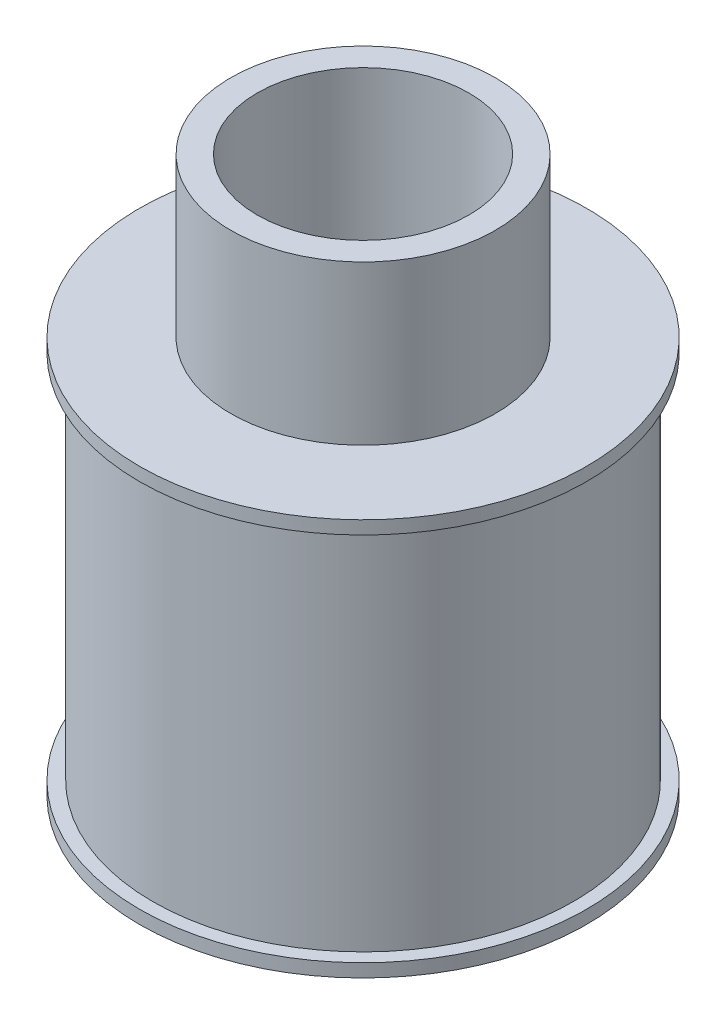
SolidWorks part; units mm, degrees
note: '?' marks a value the reader was unsure of. The reader was unsure of these and kept them because the rebuilt part matched: shared geometry of "Croquis2<2>".
ref_plane "Alzado" through (0, 0, 0) normal (1, 0, 0) x (0, 1, 0)
ref_plane "Planta" through (0, 0, 0) normal (0, 0, 1) x (0, 1, 0)
ref_plane "Vista lateral" through (0, 0, 0) normal (0, 1, 0) x (-1, 0, 0)
sketch "Croquis1" plane through (0, 0, 0) normal (0, 1, 0) x (-1, 0, 0)
  circle A0 centre (0, 0) radius 7.95
  dimension "D1" = 15.9
extrude "Saliente-Extruir1" add sketch "Croquis1" along normal mid plane 15
sketch "Croquis2" plane through (0, 7.5, 0) normal (0, 1, 0) x (-1, 0, 0)
  circle A3 centre (0, 0) radius 8.45
  dimension "D1" = 16.9
extrude "Saliente-Extruir2" add sketch "Croquis2" against normal blind 0.5
extrude "Saliente-Extruir3" add sketch "Croquis2<2>" along normal blind 0.5 from surface at -15 starting at face at (0, -7.5, 7.95)
sketch "Croquis2<2>" plane through (0, 7.5, 0) normal (0, 1, 0) x (-1, 0, 0) same geometry as "Croquis2"
sketch "Croquis3" plane through (0, -7.5, 0) normal (0, 1, 0) x (-1, 0, 0)
  circle A0 centre (0, 0) radius 5
  dimension "D1" = 10
extrude "Saliente-Extruir4" add sketch "Croquis3" along normal blind 21
sketch "Croquis4" plane through (0, -7, 0) normal (0, 1, 0) x (-1, 0, 0)
  circle A0 centre (0, 0) radius 3
  dimension "D1" = 6
extrude "Cortar-Extruir1" cut sketch "Croquis4" against normal through all both and the other way through all
sketch "Croquis5" [suppressed] plane through (0, 0, 0) normal (0, 0, 1) x (0, 1, 0)
  line L4 (10.5, 5) -> (10.5, -5) construction
  line L5 (13.5, 5) -> (7.5, 5) construction
  line L9 (7.5, -5) -> (7.5, 5) construction
  line L10 (7.5, -5) -> (7.5, 5) construction
  point P10 (10.5, 0)
sketch "Croquis6" [suppressed] plane through (0, 0, 0) normal (1, 0, 0) x (0, 1, 0)
  point P0 (10.5, 0)
hole_wizard "Taladro roscado M32" [suppressed] positions "Croquis6" profile "Croquis7" tap size "M3" standard "DIN"
sketch "Croquis7" plane through (0, 10.5, 0) normal (0, 1, 0) x (0, 0, 1)
  line L0 (0, 0) -> (0, 5)
  line L1 (0, 5) -> (1.25, 5)
  line L2 (1.25, 5) -> (1.25, 0)
  line L5 (1.25, 0) -> (0, 0)
  line L11 (0, -6.35) -> (0, 107.95) construction
  dimension "Diámetro de perforador para roscar hasta el siguiente" = 2.5
  dimension "Profundidad de perforador para roscar hasta el siguiente" = 5
cosmetic thread "Rosca de taladro1" [suppressed] parameters "D2"=3
hole_wizard "Taladro roscado M31" [suppressed] positions "Croquis5" profile "Croquis9" tap size "M3" standard "DIN"
sketch "Croquis9" plane through (0, 10.5, 0) normal (1, 0, 0) x (0, 1, 0)
  line L0 (0, 0) -> (0, 8.45)
  line L1 (0, 8.45) -> (1.25, 8.45)
  line L2 (1.25, 8.45) -> (1.25, 0)
  line L5 (1.25, 0) -> (0, 0)
  line L11 (0, -6.35) -> (0, 107.95) construction
  dimension "Diámetro de perforador para roscar hasta el siguiente" = 2.5
  dimension "Profundidad de perforador para roscar hasta el siguiente" = 8.45
cosmetic thread "Rosca de taladro2" [suppressed] parameters "D2"=3
ref_axis "Eje1" [suppressed] through (0, 10.5, 5) along (0, 0, -1)?
ref_axis "Eje2" [suppressed] through (5, 10.5, 0) along (-1, 0, 0)?
sketch "Croquis10" plane through (0, -7.5, 0) normal (0, -1, 0) x (1, 0, 0)
  circle A0 centre (0, 0) radius 4
  dimension "D1" = 8
extrude "Cortar-Extruir2" cut sketch "Croquis10" against normal through all
equation "\"Dp\"= 15.9"
equation "\"D1@Croquis1\"=\"Dp\""
equation "\"Dm\"= 10"
equation "\"De\"= \"Dp\" + 1"
equation "\"F\"= 15"
equation "\"L\"= 21"
equation "\"D1@Croquis2\"=\"De\""
equation "\"D1@Saliente-Extruir1\"=\"F\""
equation "\"D1@Saliente-Extruir4\"=\"L\""
equation "\"agujero\"= 6"
equation "\"D1@Croquis4\"=\"agujero\""
